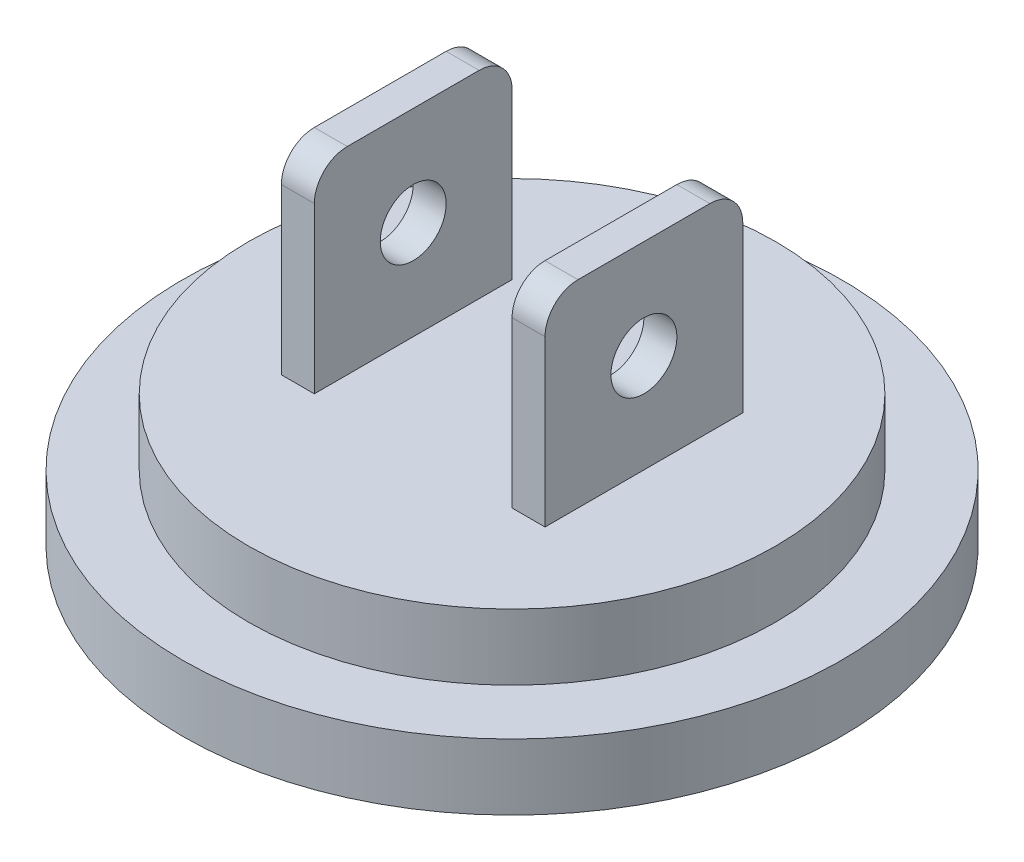
SolidWorks part; units mm, degrees
ref_plane "Front Plane" through (0, 0, 0) normal (0, 0, 1) x (1, 0, 0)
ref_plane "Top Plane" through (0, 0, 0) normal (0, 1, 0) x (1, 0, 0)
ref_plane "Right Plane" through (0, 0, 0) normal (1, 0, 0) x (0, 0, -1)
sketch "Sketch2" plane through (0, 0, 0) normal (0, 1, 0) x (1, 0, 0)
  circle A1 centre (0, 0) radius 63.5
  dimension "D2" = 127
extrude "Boss-Extrude1" add sketch "Sketch2" along normal blind 12.7
sketch "Sketch3" plane through (0, 12.7, 0) normal (0, 1, 0) x (1, 0, 0)
  circle A0 centre (0, 0) radius 50.8
  dimension "D1" = 101.6
extrude "Boss-Extrude2" add sketch "Sketch3" along normal blind 12.7
sketch "Sketch4" plane through (0, 0, 0) normal (0, -1, 0) x (1, 0, 0)
  circle A0 centre (0, 0) radius 6.35
  dimension "D1" = 12.7
extrude "Boss-Extrude3" add sketch "Sketch4" along normal blind 25.4
sketch "Sketch5" plane through (0, 25.4, 0) normal (0, 1, 0) x (1, 0, 0)
  line L0 (0, 0) -> (0, 17.7689) construction
  line L1 (25.4, -19.05) -> (19.05, -19.05)
  line L2 (-25.4, 19.05) -> (-19.05, 19.05)
  line L3 (-25.4, 19.05) -> (-25.4, -19.05)
  line L4 (-25.4, -19.05) -> (-19.05, -19.05)
  line L5 (-19.05, 19.05) -> (-19.05, -19.05)
  line L6 (19.05, 19.05) -> (19.05, -19.05)
  line L7 (25.4, 19.05) -> (19.05, 19.05)
  line L8 (25.4, 19.05) -> (25.4, -19.05)
  dimension "D1" = 6.35
  dimension "D2" = 38.1
  dimension "D3" = 19.05
  dimension "D4" = 19.05
extrude "Boss-Extrude4" add sketch "Sketch5" along normal blind 38.1
fillet "Fillet1" radius 6.35 4 edges at (22.225, 63.5, 19.05) (-22.225, 63.5, 19.05) (22.225, 63.5, -19.05) (-22.225, 63.5, -19.05)
sketch "Sketch6" plane through (-25.4, 0, 0) normal (-1, 0, 0) x (0, 0, 1)
  line L0 (-12.7, 63.5) -> (12.7, 63.5) construction
  line L1 (19.05, 57.15) -> (19.05, 25.4) construction
  circle A0 centre (0, 44.45) radius 6.35
  dimension "D1" = 12.7
  dimension "D2" = 19.05
  dimension "D3" = 19.05
extrude "Cut-Extrude1" cut sketch "Sketch6" against normal through all
sketch "Sketch7" plane through (0, -25.4, 0) normal (0, -1, 0) x (1, 0, 0)
  line L8 (0, 5.08) -> (0.7102, 6.3102)
  line L9 (0, 5.08) -> (-0.7102, 6.3102)
  arc A6 (0.7102, 6.3102) -> (-0.7102, 6.3102) centre (0, 0) ccw
extrude "Cut-Extrude2" cut sketch "Sketch7" against normal blind 12.7
pattern_circular "CirPattern1" count 28 over 360 about axis through (0, -25.4, 0) along (0, 1, 0) of "Cut-Extrude2" reverse direction yes
